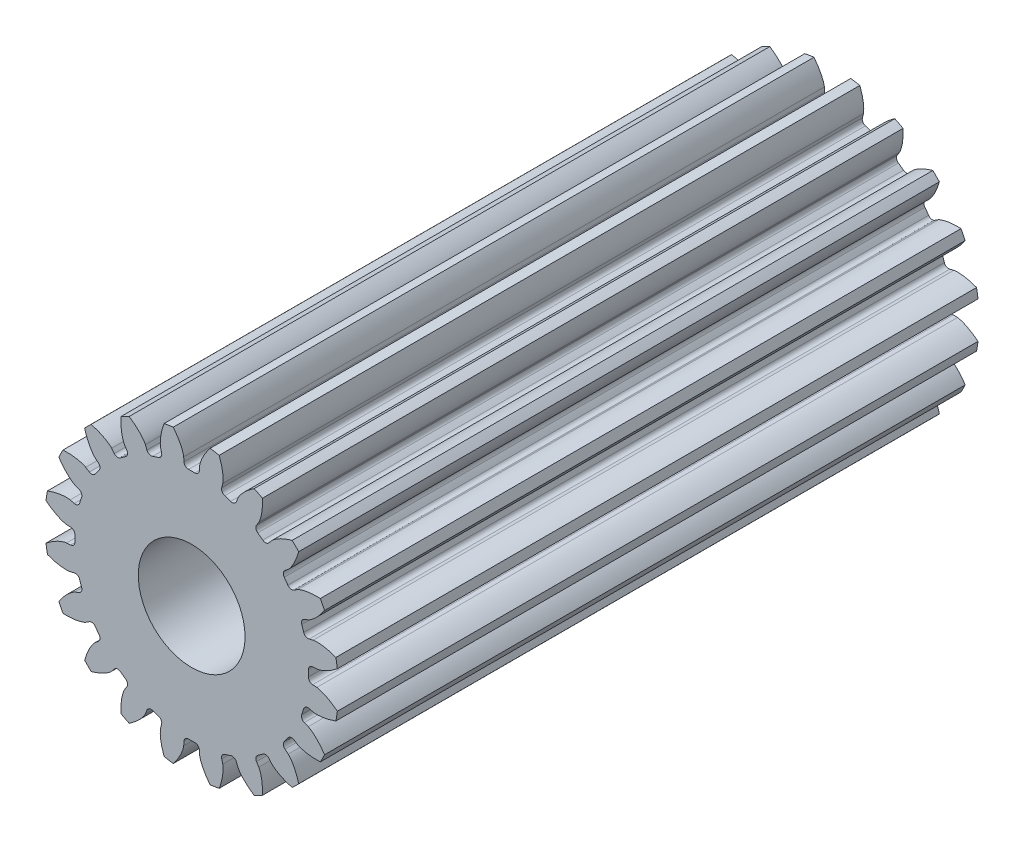
SolidWorks part; units mm, degrees
material "Plain Carbon Steel"
ref_plane "Front Plane" through (0, 0, 0) normal (0, 0, 1) x (1, 0, 0)
ref_plane "Top Plane" through (0, 0, 0) normal (0, 1, 0) x (1, 0, 0)
ref_plane "Right Plane" through (0, 0, 0) normal (1, 0, 0) x (0, 0, -1)
sketch "Sketch1" plane through (0, 0, 0) normal (0, 0, 1) x (1, 0, 0)
  line L0 (0, 0) -> (0, 7.9375) construction
  line L1 (-2.5511, 8.866) -> (2.5511, 7.009) construction
  circle A0 centre (0, 0) radius 6.9453 construction
  circle A1 centre (0, 0) radius 8.7312 construction
  circle A2 centre (0, 0) radius 7.9375 construction
  circle A3 centre (0, 0) radius 7.4588 construction
  point P8 (406.4, 0)
  point P13 (254, 0)
  dimension "OD | Outside Diameter" = 17.4625
  dimension "Root Diameter" = 13.8906
  dimension "Gear Pitch Diameter" = 15.875
  dimension "Base Diameter" = 14.9176
  dimension "Pressure Angle" = 20
  dimension "Number of Teeth" = 508
  dimension "Gear Pitch | Diametral Pitch" = 812.8
sketch "Sketch2" plane through (0, 0, 0) normal (1, 0, 0) x (0, 0, -1)
  line L0 (-19.05, 0) -> (19.05, 0) construction
  point P2 (-10.3188, 0)
  point P5 (-5.9531, 0)
  point P6 (10.3188, 0)
  dimension "Length" = 38.1
  dimension "D1" = 8.7312
  dimension "D2" = 13.0969
  dimension "D3" = 8.7312
sketch "Sketch3" plane through (0, 0, 0) normal (0, 0, 1) x (1, 0, 0)
  circle A0 centre (0, 0) radius 8.7312
  circle A1 centre (0, 0) radius 8.7312 construction
extrude "Boss-Extrude1" add sketch "Sketch3" against normal up to vertex (19.05 mm away) and the other way up to vertex (19.05 mm away) up to point (0, 0, -19.05) other way up to point (0, 0, 19.05)
sketch "Sketch4" plane through (0, 0, 0) normal (0, 0, 1) x (1, 0, 0)
  line L0 (0, 0) -> (6.9313, 0.4417) construction
  line L2 (0, 0) -> (6.9313, -0.4417) construction
  line L4 (6.9313, 0.4417) -> (7.4437, 0.4743)
  line L5 (7.4437, -0.4743) -> (6.9313, -0.4417)
  arc A0 (6.9313, 0.4417) -> (6.9313, -0.4417) centre (0, 0) cw
  arc A3 (8.6626, 1.0928) -> (8.6626, -1.0928) centre (0, 0) cw
  circle A4 centre (0, 0) radius 8.7312 construction
  spline S0 degree 4 poles (7.4437, 0.4743) (7.4457, 0.4745) (7.4515, 0.475) (7.4622, 0.4763) (7.4797, 0.4789) (7.502, 0.4828) (7.5306, 0.4887) (7.5643, 0.4966) (7.6011, 0.5063) (7.6409, 0.518) (7.6805, 0.5306) (7.7199, 0.5441) (7.7589, 0.5584) (7.806, 0.5766) (7.8621, 0.5998) (7.9274, 0.6288) (8.0008, 0.664) (8.0749, 0.7023) (8.1474, 0.742) (8.22, 0.7844) (8.2897, 0.8269) (8.3615, 0.8734) (8.4273, 0.9176) (8.5003, 0.9695) (8.5589, 1.0122) (8.6353, 1.0711) (8.6802, 1.1067) (8.7324, 1.1493) (8.7553, 1.1687) (8.7695, 1.1806) knots 0 0 0 0 0 0.005377 0.015084 0.028532 0.04661 0.064855 0.092111 0.119476 0.146842 0.174209 0.201575 0.228941 0.256307 0.307035 0.361767 0.4165 0.471232 0.525964 0.580697 0.635429 0.690161 0.744894 0.799626 0.854358 0.909091 0.954545 1 1 1 1 1 construction
  spline S1 degree 4 poles (7.4437, 0.4743) (7.4457, 0.4745) (7.4515, 0.475) (7.4622, 0.4763) (7.4797, 0.4789) (7.502, 0.4828) (7.5306, 0.4887) (7.5643, 0.4966) (7.6011, 0.5063) (7.6409, 0.518) (7.6805, 0.5306) (7.7199, 0.5441) (7.7589, 0.5584) (7.806, 0.5766) (7.8621, 0.5998) (7.9274, 0.6288) (8.0008, 0.664) (8.0749, 0.7023) (8.1474, 0.742) (8.22, 0.7844) (8.2897, 0.8269) (8.3615, 0.8734) (8.4273, 0.9176) (8.5003, 0.9695) (8.5589, 1.0122) (8.6188, 1.0583) (8.6478, 1.0811) (8.6626, 1.0928) knots 0 0 0 0 0 0.005377 0.015084 0.028532 0.04661 0.064855 0.092111 0.119476 0.146842 0.174209 0.201575 0.228941 0.256307 0.307035 0.361767 0.4165 0.471232 0.525964 0.580697 0.635429 0.690161 0.744894 0.799626 0.854358 0.909091 0.909091 0.909091 0.909091 0.909091
  spline S2 degree 4 poles (7.4437, -0.4743) (7.4457, -0.4745) (7.4515, -0.475) (7.4622, -0.4763) (7.4797, -0.4789) (7.502, -0.4828) (7.5306, -0.4887) (7.5643, -0.4966) (7.6011, -0.5063) (7.6409, -0.518) (7.6805, -0.5306) (7.7199, -0.5441) (7.7589, -0.5584) (7.806, -0.5766) (7.8621, -0.5998) (7.9274, -0.6288) (8.0008, -0.664) (8.0749, -0.7023) (8.1474, -0.742) (8.22, -0.7844) (8.2897, -0.8269) (8.3615, -0.8734) (8.4273, -0.9176) (8.5003, -0.9695) (8.5589, -1.0122) (8.6353, -1.0711) (8.6802, -1.1067) (8.7324, -1.1493) (8.7553, -1.1687) (8.7695, -1.1806) knots 0 0 0 0 0 0.005377 0.015084 0.028532 0.04661 0.064855 0.092111 0.119476 0.146842 0.174209 0.201575 0.228941 0.256307 0.307035 0.361767 0.4165 0.471232 0.525964 0.580697 0.635429 0.690161 0.744894 0.799626 0.854358 0.909091 0.954545 1 1 1 1 1 construction
  spline S3 degree 4 poles (7.4437, -0.4743) (7.4457, -0.4745) (7.4515, -0.475) (7.4622, -0.4763) (7.4797, -0.4789) (7.502, -0.4828) (7.5306, -0.4887) (7.5643, -0.4966) (7.6011, -0.5063) (7.6409, -0.518) (7.6805, -0.5306) (7.7199, -0.5441) (7.7589, -0.5584) (7.806, -0.5766) (7.8621, -0.5998) (7.9274, -0.6288) (8.0008, -0.664) (8.0749, -0.7023) (8.1474, -0.742) (8.22, -0.7844) (8.2897, -0.8269) (8.3615, -0.8734) (8.4273, -0.9176) (8.5003, -0.9695) (8.5589, -1.0122) (8.6188, -1.0583) (8.6478, -1.0811) (8.6626, -1.0928) knots 0 0 0 0 0 0.005377 0.015084 0.028532 0.04661 0.064855 0.092111 0.119476 0.146842 0.174209 0.201575 0.228941 0.256307 0.307035 0.361767 0.4165 0.471232 0.525964 0.580697 0.635429 0.690161 0.744894 0.799626 0.854358 0.909091 0.909091 0.909091 0.909091 0.909091
  dimension "D1" = 13.8906
extrude "Cut-Extrude1" cut sketch "Sketch4" against normal through all both and the other way through all
fillet "Fillet1" radius 0.2663 2 edges at (6.9313, -0.4417, 0) (6.9313, 0.4417, 0)
pattern_circular "CirPattern1" count 20 over 360 about axis through (0, 0, 19.05) along (0, 0, -1) of "Cut-Extrude1", "Fillet1"
sketch "Sketch5" plane through (0, 0, 19.05) normal (0, 0, 1) x (1, 0, 0)
  point P0 (0, 0)
hole_wizard "1/4 (0.2500) Dowel Hole1" positions "Sketch5" profile "Sketch6" hole size "1/4" standard "ANSI Inch" end condition through all
sketch "Sketch6" plane through (0, 0, 19.05) normal (1, 0, 0) x (0, -1, 0)
  line L0 (0, 0) -> (0, 38.1)
  line L1 (0, 38.1) -> (3.175, 38.1)
  line L2 (3.175, 38.1) -> (3.175, 0)
  line L5 (3.175, 0) -> (0, 0)
  line L11 (0, -6.35) -> (0, 107.95) construction
  dimension "Thru Hole Dia." = 6.35
  dimension "Thru Hole Depth" = 38.1
equation "\"Root Diameter@Sketch1\"=\"Root Diameter\""
equation "\"OD | Outside Diameter@Sketch1\"=\"Outside Diameter\""
equation "\"D1@CirPattern1\"=\"Number of Teeth\""
equation "\"Diametral Pitch\"=32"
equation "\"Number of Teeth\"= 20"
equation "\"Pressure Angle\"=20"
equation "\"Pitch Diameter\"= \"Number of Teeth\" / \"Diametral Pitch\""
equation "\"Base Diameter\"= \"Pitch Diameter\" * cos ( \"Pressure Angle\" )"
equation "\"Outside Diameter\"= ( \"Number of Teeth\" + 2 ) / \"Diametral Pitch\""
equation "\"Dedendum\"= 1.25 / \"Diametral Pitch\""
equation "\"Root Diameter\"= \"Pitch Diameter\" - ( 2 * \"Dedendum\" )"
equation "\"Pitch Angle\"= 360deg / \"Number of Teeth\""
equation "\"Alpha\"= sqr ( \"Pitch Diameter\" ^ 2 - \"Base Diameter\" ^ 2 ) / \"Base Diameter\" * 180 / PI - \"Pressure Angle\""
equation "\"Beta\"= ( \"Pitch Angle\" / 4 - \"Alpha\" )"
equation "\"Phi\"= sqr ( ( \"Outside Diameter\" / 2 ) ^ 2 - ( \"Base Diameter\" / 2 ) ^ 2 ) / ( \"Base Diameter\" / 2 )"
equation "\"Addendum\"= 1 / \"Diametral Pitch\""
equation "\"WorkingDepth\"= 2 / \"Diametral Pitch\""
equation "\"WholeDepth\"= 2.25 / \"Diametral Pitch\""
equation "\"Clearance\"= 0.25 / \"Diametral Pitch\""
equation "\"ToothThickness\"= ( pi * 2 ) / \"Diametral Pitch\""
equation "\"CircularPitch\"= pi / \"Diametral Pitch\""
equation "\"Number of Teeth@Sketch1\"=\"Number of Teeth\""
equation "\"Gear Pitch | Diametral Pitch@Sketch1\"=\"Diametral Pitch\""
equation "\"Pressure Angle@Sketch1\"=\"Pressure Angle\""
equation "\"Gear Pitch Diameter@Sketch1\"=\"Pitch Diameter\""
equation "\"Base Diameter@Sketch1\"=\"Base Diameter\""
equation "\"Fillet\"= \"Clearance\" * cos ( \"Pressure Angle\" ) * tan ( ( 90 + \"Pressure Angle\" ) / 2 )"
equation "\"D1@Fillet1\"=\"Fillet\""
equation "\"D1@Sketch4\"=if( \"Base Diameter\">\"Root Diameter\",\"Root Diameter\",\"Base Diameter\"-.00001)"
equation "\"D1@Sketch2\"=\"OD | Outside Diameter@Sketch1\"*2*0.5*0.5"
equation "\"D2@Sketch2\"=\"D1@Sketch2\"*1.5"
equation "\"D3@Sketch2\"=\"D1@Sketch2\""
equation "\"Length\" = 1.5in"
equation "\"Length@Sketch2\"= \"Length\""
